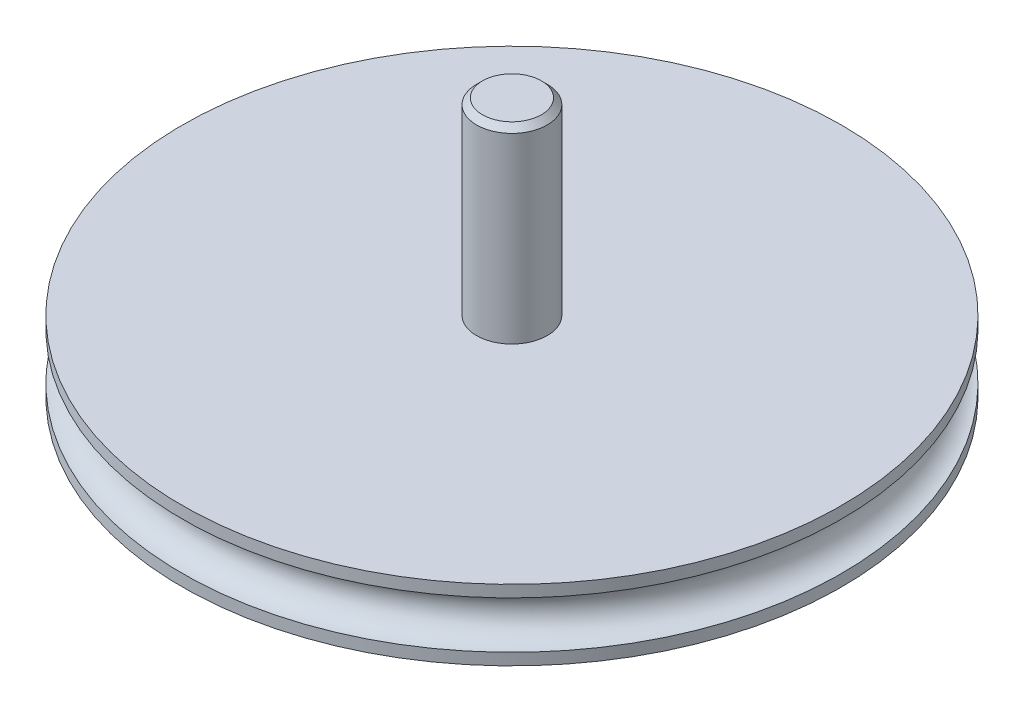
SolidWorks part; units mm, degrees
ref_plane "Plan de face" through (0, 0, 0) normal (0, 0, 1) x (1, 0, 0)
ref_plane "Plan de dessus" through (0, 0, 0) normal (0, 1, 0) x (1, 0, 0)
ref_plane "Plan de droite" through (0, 0, 0) normal (1, 0, 0) x (0, 0, -1)
sketch "Esquisse1" plane through (0, 0, 0) normal (0, 1, 0) x (1, 0, 0)
  circle A0 centre (0, 0) radius 3
  dimension "D1" = 6
extrude "Boss.-Extru.1" add sketch "Esquisse1" along normal blind 16
sketch "Esquisse4" plane through (0, 0, 0) normal (1, 0, 0) x (0, 0, -1)
  line L0 (0, 0) -> (28, 0)
  line L1 (28, 0) -> (28, -6) construction
  line L2 (28, -6) -> (0, -6)
  line L3 (0, -6) -> (0, 0)
  line L4 (28, -1) -> (28, 0)
  line L5 (28, -5) -> (28, -6)
  arc A0 (28, -1) -> (28, -5) centre (28, -3) ccw
  point P8 (28, -3)
  dimension "D3" = 2
  dimension "D1" = 6
  dimension "D2" = 28
revolve "Révolution1" add sketch "Esquisse4" angle 360 about L3
chamfer "Chanfrein1" distance 0.5 angle 45 1 edges at (0, 16, 3)
ref_axis "Axe1" through (0, 15.5, 0) along (0, -1, 0)
